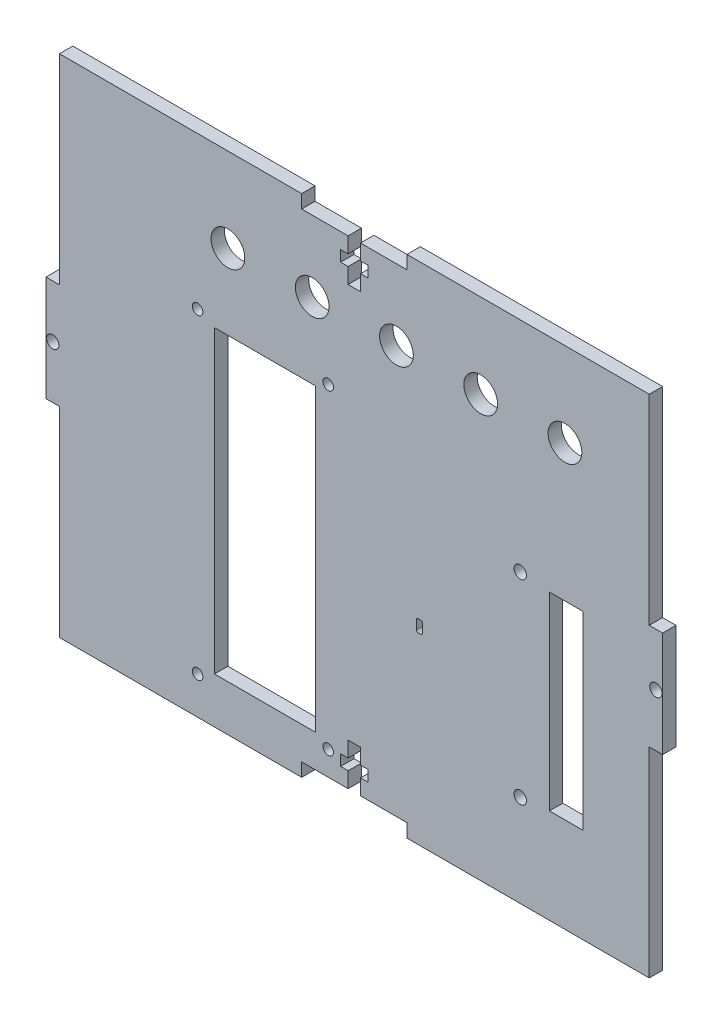
SolidWorks part; units mm, degrees
ref_plane "Front Plane" through (0, 0, 0) normal (0, 0, 1) x (1, 0, 0)
ref_plane "Top Plane" through (0, 0, 0) normal (0, 1, 0) x (1, 0, 0)
ref_plane "Right Plane" through (0, 0, 0) normal (1, 0, 0) x (0, 0, -1)
sketch "Sketch1" plane through (0, 0, 0) normal (0, 0, 1) x (1, 0, 0)
  line L0 (0, 60) -> (0, -60) construction
  line L1 (-70, 60) -> (70, 60)
  line L2 (-70, 60) -> (-70, -60)
  line L3 (-70, -60) -> (70, -60)
  line L4 (70, 60) -> (70, -60)
  line L5 (-70, 60) -> (70, -60) construction
  line L6 (-70, -60) -> (70, 60) construction
  line L7 (-70, 0) -> (70, 0) construction
  line L8 (-3.25, -50.525) -> (3.25, -50.525)
  line L9 (12.5, 60) -> (-12.5, 60)
  line L10 (12.5, 60) -> (12.5, 56.825)
  line L11 (12.5, 56.825) -> (-12.5, 56.825)
  line L12 (-12.5, 60) -> (-12.5, 56.825)
  line L13 (12.5, 60) -> (-12.5, 56.825) construction
  line L14 (12.5, 56.825) -> (-12.5, 60) construction
  line L15 (-1.47, 56.825) -> (1.47, 56.825)
  line L16 (-1.47, 56.825) -> (-1.47, 46.825)
  line L17 (-1.47, 46.825) -> (1.47, 46.825)
  line L18 (1.47, 56.825) -> (1.47, 46.825)
  line L19 (-1.47, 56.825) -> (1.47, 46.825) construction
  line L20 (-1.47, 46.825) -> (1.47, 56.825) construction
  line L21 (-3.25, 53.125) -> (3.25, 53.125)
  line L22 (-3.25, 53.125) -> (-3.25, 50.525)
  line L23 (-3.25, 50.525) -> (3.25, 50.525)
  line L24 (3.25, 53.125) -> (3.25, 50.525)
  line L25 (-3.25, 53.125) -> (3.25, 50.525) construction
  line L26 (-3.25, 50.525) -> (3.25, 53.125) construction
  line L27 (3.25, -53.125) -> (3.25, -50.525)
  line L28 (-3.25, -53.125) -> (3.25, -53.125)
  line L29 (-3.25, -53.125) -> (-3.25, -50.525)
  line L30 (-1.47, -46.825) -> (1.47, -46.825)
  line L31 (1.47, -56.825) -> (1.47, -46.825)
  line L32 (-1.47, -56.825) -> (1.47, -56.825)
  line L33 (-1.47, -56.825) -> (-1.47, -46.825)
  line L34 (12.5, -56.825) -> (-12.5, -56.825)
  line L35 (-12.5, -60) -> (-12.5, -56.825)
  line L36 (12.5, -60) -> (-12.5, -60)
  line L37 (12.5, -60) -> (12.5, -56.825)
  line L38 (73.175, -12.5) -> (70, -12.5)
  line L39 (-73.175, 12.5) -> (-70, 12.5)
  line L40 (-73.175, 12.5) -> (-73.175, -12.5)
  line L41 (-73.175, -12.5) -> (-70, -12.5)
  line L42 (-70, 12.5) -> (-70, -12.5)
  line L43 (-73.175, 12.5) -> (-70, -12.5) construction
  line L44 (-73.175, -12.5) -> (-70, 12.5) construction
  line L45 (70, 12.5) -> (70, -12.5)
  line L46 (73.175, 12.5) -> (70, 12.5)
  line L47 (73.175, 12.5) -> (73.175, -12.5)
  circle A0 centre (-71.5875, 0) radius 1.47
  circle A1 centre (71.5875, 0) radius 1.47
  point P0 (0, 0)
  point P10 (0, 58.4125)
  point P15 (0, 51.825)
  point P20 (0, 51.825)
  point P37 (-71.5875, 0)
  dimension "D11" = 2.94
  dimension "D1" = 120
  dimension "D2" = 140
  dimension "D3" = 3.175
  dimension "D4" = 10
  dimension "D5" = 2.94
  dimension "D6" = 25
  dimension "D7" = 6.5
  dimension "D8" = 2.6
  dimension "D9" = 6.3
  dimension "D10" = 3.175
extrude "Boss-Extrude1" add sketch "Sketch1" along normal mid plane 3.175 contours L21 L24 L23 L18 L17 L16 L22 L11 L12 L1 L2 L3 L4 L10 | L40 L39 L42 L41 | A0 | L38 L45 L46 L47 | A1 region at (0, 0, 0)
sketch "Sketch3" plane through (0, 0, -1.5875) normal (0, 0, -1) x (-1, 0, 0)
  line L0 (-9.6476, 0) -> (-9.6476, -15) construction
  line L5 (-9.6476, -15) -> (-19.2951, -15) construction
  line L6 (-50.3, 7.5) -> (-50.3, -22.5) construction
  line L7 (-46.3, 7.5) -> (-54.3, 7.5)
  line L8 (-46.3, 7.5) -> (-46.3, -37.5)
  line L9 (-46.3, -37.5) -> (-54.3, -37.5)
  line L10 (-54.3, 7.5) -> (-54.3, -37.5)
  line L11 (-48.7125, -40) -> (-48.7125, 10) construction
  line L12 (-51.8875, 10) -> (-51.8875, -40) construction
  line L13 (0, 0) -> (-19.2951, 0) construction
  dimension "D1" = 8
  dimension "D2" = 45
  dimension "D3" = 15
extrude "Cut-Extrude1" cut sketch "Sketch3" against normal through all
sketch "Sketch4" plane through (0, 0, -1.5875) normal (0, 0, -1) x (-1, 0, 0)
  line L0 (33.2, 21.2555) -> (33.2, -48.2445) construction
  line L1 (33.2, 22.1055) -> (9.2, 22.1055)
  line L2 (33.2, 22.1055) -> (33.2, -49.0945)
  line L3 (33.2, -49.0945) -> (9.2, -49.0945)
  line L4 (9.2, 22.1055) -> (9.2, -49.0945)
  line L5 (9.2, -48.2445) -> (9.2, 21.2555) construction
  line L6 (10.05, 22.1055) -> (16.7, 22.1055) construction
  line L7 (32.35, -49.0945) -> (10.05, -49.0945) construction
extrude "Cut-Extrude2" cut sketch "Sketch4" against normal through all
sketch "Sketch5" plane through (0, 0, -1.5875) normal (0, 0, -1) x (-1, 0, 0)
  line L0 (-15.1534, -16.25) -> (-15.7792, -16.25) construction
  line L1 (-15.7792, -13.75) -> (-15.1534, -13.75) construction
  line L2 (-14.9534, -13.95) -> (-14.9534, -16.05) construction
  line L3 (-15.1534, -16.25) -> (-15.7792, -16.25)
  line L4 (-15.7792, -13.75) -> (-15.1534, -13.75)
  line L5 (-14.9534, -13.95) -> (-14.9534, -16.05)
  line L6 (-15.1534, -16.45) -> (-15.7792, -16.45)
  line L7 (-15.7792, -13.55) -> (-15.1534, -13.55)
  line L8 (-14.7534, -13.95) -> (-14.7534, -16.05)
  arc A0 (-15.1534, -16.25) -> (-14.9534, -16.05) centre (-15.1534, -16.05) ccw construction
  arc A1 (-15.9775, -16.0753) -> (-15.7792, -16.25) centre (-15.7792, -16.05) ccw construction
  arc A2 (-15.9775, -13.9247) -> (-15.9775, -16.0753) centre (-7.5458, -15) ccw construction
  arc A3 (-15.7792, -13.75) -> (-15.9775, -13.9247) centre (-15.7792, -13.95) ccw construction
  arc A4 (-14.9534, -13.95) -> (-15.1534, -13.75) centre (-15.1534, -13.95) ccw construction
  arc A5 (-15.1534, -16.25) -> (-14.9534, -16.05) centre (-15.1534, -16.05) ccw
  arc A6 (-15.9775, -16.0753) -> (-15.7792, -16.25) centre (-15.7792, -16.05) ccw
  arc A7 (-15.9775, -13.9247) -> (-15.9775, -16.0753) centre (-7.5458, -15) ccw
  arc A8 (-15.7792, -13.75) -> (-15.9775, -13.9247) centre (-15.7792, -13.95) ccw
  arc A9 (-14.9534, -13.95) -> (-15.1534, -13.75) centre (-15.1534, -13.95) ccw
  arc A10 (-16.1759, -16.1006) -> (-15.7792, -16.45) centre (-15.7792, -16.05) ccw
  arc A11 (-16.1759, -13.8994) -> (-16.1759, -16.1006) centre (-7.5458, -15) ccw
  arc A12 (-15.7792, -13.55) -> (-16.1759, -13.8994) centre (-15.7792, -13.95) ccw
  arc A13 (-14.7534, -13.95) -> (-15.1534, -13.55) centre (-15.1534, -13.95) ccw
  arc A14 (-15.1534, -16.45) -> (-14.7534, -16.05) centre (-15.1534, -16.05) ccw
  dimension "D1" = 0.2
extrude "Cut-Extrude4" cut sketch "Sketch5" against normal through all contours L8 A14 L6 A10 A11 A12 L7 A13
sketch "Sketch6" plane through (0, 0, -1.5875) normal (0, 0, -1) x (-1, 0, 0)
  line L0 (-70, 40) -> (70, 40) construction
  line L1 (-70, 56.825) -> (-70, 12.5) construction
  line L2 (70, 60) -> (70, 12.5) construction
  line L3 (70, 60) -> (12.5, 60) construction
  line L4 (-50, 40) -> (-30, 40)
  line L5 (-30, 40) -> (-10, 40)
  line L6 (-10, 40) -> (10, 40)
  line L7 (10, 40) -> (30, 40)
  line L8 (-70, 60) -> (-70, 12.5) construction
  line L9 (-10, 40) -> (10, 40)
  line L10 (-30, 40) -> (-10, 40)
  line L11 (-50, 40) -> (-30, 40)
  line L12 (-70, 40) -> (-50, 40)
  circle A0 centre (30, 40) radius 4
  circle A1 centre (10, 40) radius 4
  circle A2 centre (-10, 40) radius 4
  circle A3 centre (-30, 40) radius 4
  circle A4 centre (-50, 40) radius 4
  dimension "D4" = 8
  dimension "D1" = 20
  dimension "D2" = 20
  dimension "D3" = 20
  dimension "D5" = 5
extrude "Cut-Extrude5" cut sketch "Sketch6" against normal through all contours A0 | A1 | A2 | A3 | A4
sketch "Sketch9" plane through (0, 0, 1.5875) normal (0, 0, 1) x (1, 0, 0)
  circle A0 centre (-37.2, 23.9055) radius 1.25 construction
  circle A1 centre (-6.2, 23.9055) radius 1.25 construction
  circle A2 centre (-6.2, -51.0945) radius 1.25 construction
  circle A3 centre (-37.2, -51.0945) radius 1.25 construction
  circle A4 centre (-37.2, 23.9055) radius 1.25
  circle A5 centre (-6.2, 23.9055) radius 1.25
  circle A6 centre (-6.2, -51.0945) radius 1.25
  circle A7 centre (-37.2, -51.0945) radius 1.25
  circle A8 centre (39.3875, 8.1613) radius 1.47 construction
  circle A9 centre (39.3875, -38.1613) radius 1.47 construction
  circle A10 centre (39.3875, 8.1613) radius 1.47
  circle A11 centre (39.3875, -38.1613) radius 1.47
extrude "Cut-Extrude6" cut sketch "Sketch9" against normal through all
sketch "Sketch10" plane through (0, 0, -1.5875) normal (0, 0, -1) x (-1, 0, 0)
  line L4 (50, 60) -> (50, -60) construction
  line L5 (70, 60) -> (12.5, 60) construction
  line L6 (70, -60) -> (12.5, -60) construction
  line L7 (70, 60) -> (70, 12.5) construction
  text T0 "Alden Dent PID Box" font "Century Gothic" height 9
  dimension "D1" = 20
